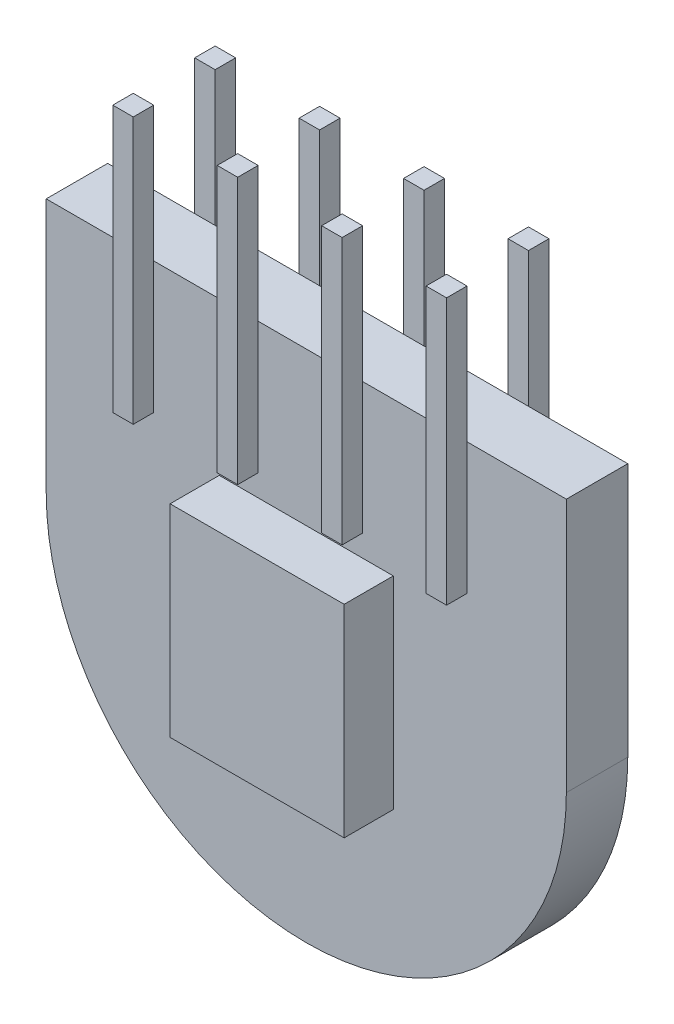
SolidWorks part; units mm, degrees
ref_plane "Přední rovina" through (0, 0, 0) normal (0, 0, 1) x (1, 0, 0)
ref_plane "Horní rovina" through (0, 0, 0) normal (0, 1, 0) x (1, 0, 0)
ref_plane "Pravá rovina" through (0, 0, 0) normal (1, 0, 0) x (0, 0, -1)
sketch "Skica1" plane through (0, 0, 0) normal (0, 0, 1) x (1, 0, 0)
  line L0 (-6.35, 0) -> (-6.35, 12.5)
  line L1 (-2.125, 2.47) -> (2.125, 2.47)
  line L2 (-2.125, 2.47) -> (-2.125, -2.47)
  line L3 (-2.125, -2.47) -> (2.125, -2.47)
  line L4 (2.125, 2.47) -> (2.125, -2.47)
  line L5 (-2.125, 2.47) -> (2.125, -2.47) construction
  line L6 (-2.125, -2.47) -> (2.125, 2.47) construction
  line L7 (-6.35, 12.5) -> (6.35, 12.5)
  line L8 (6.35, 12.5) -> (6.35, 0)
  line L9 (0, 2.47) -> (0, -2.47) construction
  arc A0 (-6.35, 0) -> (6.35, 0) centre (0, 0) ccw
  dimension "D1" = 12.7
  dimension "D2" = 2.125
  dimension "D3" = 12.5
  dimension "D4" = 4.94
extrude "Přidat vysunutím1" add sketch "Skica1" along normal blind 1.5 contours L4 L1 L2 L3 | A0 L1 L4 L3 L2 region at (0, 4.0851, 0) region at (0, 0, 0)
extrude "Přidat vysunutím2" add sketch "Skica1<3>" along normal blind 1.2 from surface contours L4 L1 L2 L3 region at (0, 0, 0) starting at face at (0, 4.6625, 1.5)
sketch "Skica1<3>" plane through (0, 0, 0) normal (0, 0, 1) x (1, 0, 0) same geometry as "Skica1"
sketch "Skica2" plane through (0, 0, 2.7) normal (0, 0, 1) x (1, 0, 0)
  line L0 (-2.125, 2.47) -> (2.125, -2.47) construction
  line L1 (2.125, 2.47) -> (-2.125, -2.47) construction
  point P8 (0, 0)
sketch "Skica3" plane through (0, 12.5, 0) normal (0, 1, 0) x (1, 0, 0)
  line L1 (-6.35, -1.5) -> (6.35, -1.5)
  line L2 (-6.35, -1.5) -> (-6.35, 0)
  line L3 (-6.35, 0) -> (6.35, 0)
  line L4 (6.35, -1.5) -> (6.35, 0)
extrude "Odebrat vysunutím1" cut sketch "Skica3" against normal blind 3.5
sketch "Skica4" plane through (0, 9, 0) normal (0, 1, 0) x (1, 0, 0)
  line L1 (-6.35, -1.5) -> (6.35, -1.5)
  line L2 (-6.35, -1.5) -> (-6.35, 0)
  line L3 (-6.35, 0) -> (6.35, 0)
  line L4 (6.35, -1.5) -> (6.35, 0)
extrude "Odebrat vysunutím2" cut sketch "Skica4" against normal blind 5.5
ref_plane "Rovina1" through (0, 0, 0.75) normal (0, 0, 1) x (1, 0, 0)
sketch "Skica7" plane through (0, 3.5, 0) normal (0, 1, 0) x (1, 0, 0)
  line L1 (-6.35, -1.5) -> (6.35, -1.5)
  line L2 (-6.35, -1.5) -> (-6.35, 0)
  line L3 (-6.35, 0) -> (6.35, 0)
  line L4 (6.35, -1.5) -> (6.35, 0)
extrude "Přidat vysunutím5" add sketch "Skica7" along normal blind 2.7055
sketch "Skica12" plane through (0, 0, 0) normal (0, 1, 0) x (1, 0, 0)
  line L0 (6.35, 0) -> (-6.35, 0) construction
  line L1 (3.425, 0) -> (4.225, 0)
  line L2 (3.425, 0) -> (3.425, 0.8)
  line L3 (3.425, 0.8) -> (4.225, 0.8)
  line L4 (4.225, 0) -> (4.225, 0.8)
  dimension "D1" = 0.8
  dimension "D2" = 0.8
  dimension "D3" = 2.125
sketch "Skica15" plane through (0, 0, 0) normal (0, 1, 0) x (1, 0, 0)
  line L0 (-6.35, -1.5) -> (6.35, -1.5) construction
  line L1 (-4.225, -1.5) -> (-3.725, -1.5)
  line L2 (-4.225, -1.5) -> (-4.225, -2)
  line L3 (-4.225, -2) -> (-3.725, -2)
  line L4 (-3.725, -1.5) -> (-3.725, -2)
  line L5 (-6.35, 0) -> (-6.35, -1.5) construction
  dimension "D1" = 0.5
  dimension "D2" = 2.125
ref_plane "Rovina2" through (0, 3.47, 0) normal (0, 1, 0) x (1, 0, 0)
extrude "Přidat vysunutím14" add sketch "Skica15" along normal blind 6.5 from offset 3
pattern_linear "LinPole3" count 4 spacing 2.55 along (1, 0, 0) of "Přidat vysunutím14"
pattern_linear "LinPole4" count 2 spacing 2 along (0, 0, -1) of "LinPole3"
